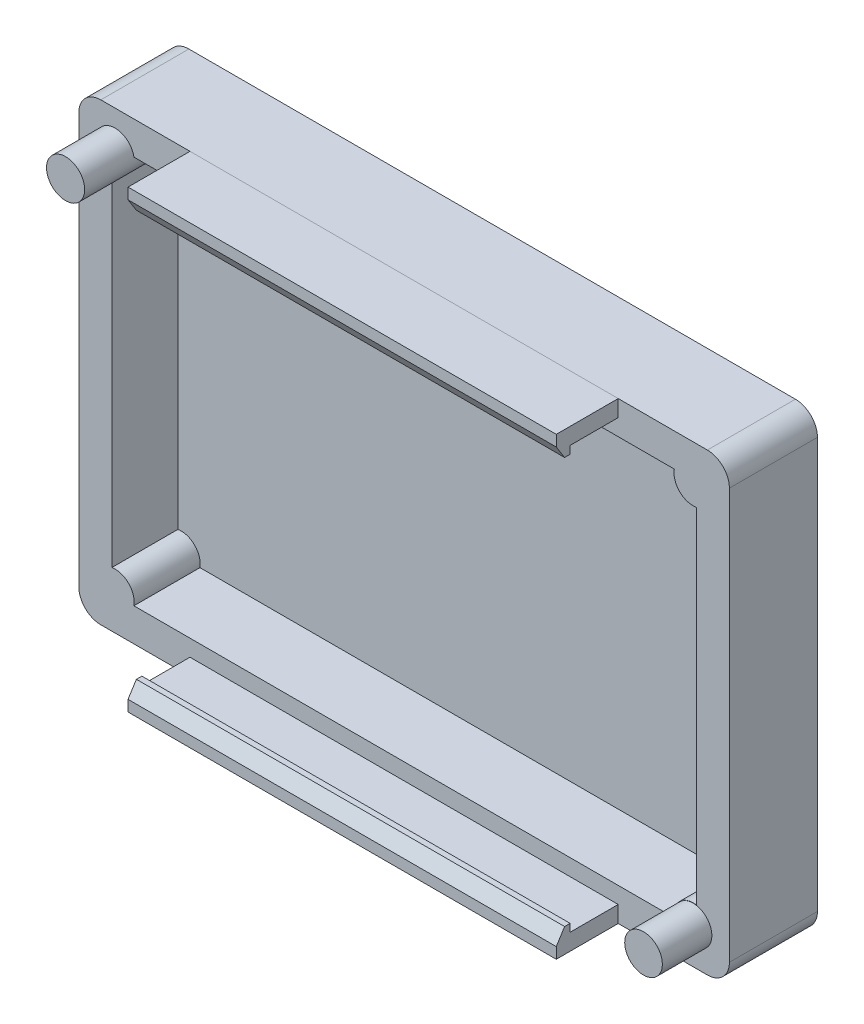
SolidWorks part; units mm, degrees
ref_plane "Płaszczyzna przednia" through (0, 0, 0) normal (0, 0, 1) x (1, 0, 0)
ref_plane "Płaszczyzna górna" through (0, 0, 0) normal (0, 1, 0) x (1, 0, 0)
ref_plane "Płaszczyzna prawa" through (0, 0, 0) normal (1, 0, 0) x (0, 0, -1)
sketch "Szkic1" plane through (0, 0, 48.1425) normal (0, 0, -1) x (-1, 0, 0)
  line L0 (25.6891, 14.5045) -> (25.6891, -16.1313) construction
  line L1 (23.6569, -18.1633) -> (-24.7789, -18.1633) construction
  line L2 (-26.8109, -16.1315) -> (-26.8109, 14.5047) construction
  line L3 (-24.7791, 16.5367) -> (23.6571, 16.5367) construction
  line L4 (25.6891, 14.5045) -> (25.6891, -16.1313)
  line L5 (23.6569, -18.1633) -> (-24.7789, -18.1633)
  line L6 (-26.8109, -16.1315) -> (-26.8109, 14.5047)
  line L7 (-24.7791, 16.5367) -> (23.6571, 16.5367)
  line L8 (-25.1053, 16.8367) -> (23.9833, 16.8367)
  line L9 (25.9891, 14.8307) -> (25.9891, -16.4575)
  line L10 (23.9831, -18.4633) -> (-25.1051, -18.4633)
  line L11 (-27.1109, -16.4577) -> (-27.1109, 14.8309)
  line L13 (-30.1109, -21.4633) -> (28.9891, -21.4633)
  line L14 (-30.1109, -21.4633) -> (-30.1109, 19.8367)
  line L15 (-30.1109, 19.8367) -> (28.9891, 19.8367)
  line L16 (28.9891, -21.4633) -> (28.9891, 19.8367)
  arc A0 (23.6571, 16.5367) -> (25.6891, 14.5045) centre (25.6891, 16.5365) ccw construction
  arc A1 (25.6891, -16.1313) -> (23.6569, -18.1633) centre (25.6891, -18.1635) ccw construction
  arc A2 (-24.7789, -18.1633) -> (-26.8109, -16.1315) centre (-26.8109, -18.1635) ccw construction
  arc A3 (-26.8109, 14.5047) -> (-24.7791, 16.5367) centre (-26.8109, 16.5365) ccw construction
  arc A4 (23.6571, 16.5367) -> (25.6891, 14.5045) centre (25.6891, 16.5365) ccw
  arc A5 (25.6891, -16.1313) -> (23.6569, -18.1633) centre (25.6891, -18.1635) ccw
  arc A6 (-24.7789, -18.1633) -> (-26.8109, -16.1315) centre (-26.8109, -18.1635) ccw
  arc A7 (-26.8109, 14.5047) -> (-24.7791, 16.5367) centre (-26.8109, 16.5365) ccw
  arc A8 (23.9833, 16.8367) -> (25.9891, 14.8307) centre (25.6891, 16.5365) ccw
  arc A9 (25.9891, -16.4575) -> (23.9831, -18.4633) centre (25.6891, -18.1635) ccw
  arc A10 (-25.1051, -18.4633) -> (-27.1109, -16.4577) centre (-26.8109, -18.1635) ccw
  arc A11 (-27.1109, 14.8309) -> (-25.1053, 16.8367) centre (-26.8109, 16.5365) ccw
  dimension "D2" = 3
  dimension "D3" = 3
  dimension "D4" = 3
  dimension "D5" = 3
  dimension "D1" = 0.3
extrude "Dodanie-wyciągnięcie1" add sketch "Szkic1" against normal blind 6 contours L13 L16 L15 L14 L11 A11 L8 A8 L9 A9 L10 A10 region at (29.3899, -0.8133, 48.1425)
sketch "Szkic2" plane through (0, 0, 48.1425) normal (0, 0, -1) x (-1, 0, 0)
  line L1 (-30.1109, 19.8367) -> (28.9891, 19.8367)
  line L2 (-30.1109, 19.8367) -> (-30.1109, -21.4633)
  line L3 (-30.1109, -21.4633) -> (28.9891, -21.4633)
  line L4 (28.9891, 19.8367) -> (28.9891, -21.4633)
extrude "Dodanie-wyciągnięcie2" add sketch "Szkic2" along normal blind 2
sketch "Szkic5" plane through (30.1109, 0, 0) normal (1, 0, 0) x (0, 0, -1)
  line L0 (-54.1425, 19.8367) -> (-59.7689, 19.8367)
  line L1 (-59.7689, 19.8367) -> (-59.7689, 18.8367)
  line L3 (-58.5127, 17.6367) -> (-58.5127, 18.3367)
  line L4 (-58.5127, 18.3367) -> (-54.1425, 18.3367)
  line L5 (-54.1425, -21.4633) -> (-54.1425, 19.8367) construction
  line L6 (-58.5127, 17.6367) -> (-59.0127, 17.6367)
  line L7 (-59.0127, 17.6367) -> (-59.7689, 18.8367)
  line L8 (-54.1425, 18.3367) -> (-54.1425, 19.8367)
  dimension "D1" = 1
  dimension "D2" = 0.7
  dimension "D3" = 5.6264
  dimension "D4" = 1.5
  dimension "D5" = 0.5
extrude "Dodanie-wyciągnięcie3" add sketch "Szkic5" against normal blind 49
extrude "Wytnij-wyciągnięcie2" cut sketch "Szkic5<2>" against normal blind 10.1
sketch "Szkic5<2>" plane through (30.1109, 0, 0) normal (1, 0, 0) x (0, 0, -1) same geometry as "Szkic5"
ref_point "Punkt1"
ref_axis "Oś1" through (30.1109, 19.8367, 54.1425) along (0, 0, -1)
ref_point "Punkt2"
ref_axis "Oś2" through (30.1109, -0.8133, 50.1425) along (0, 0, -1)
ref_plane "Płaszczyzna1" through (0, -0.8133, 0) normal (0, -1, 0) x (0, 0, -1)
mirror "Lustro3" about plane through (0, -0.8133, 0) normal (0, -1, 0) of bodies 105
sketch "Szkic10" plane through (0, 0, 54.1425) normal (0, 0, 1) x (1, 0, 0)
  circle A2 centre (26.8109, -18.1635) radius 1.7089
  circle A3 centre (-25.6891, 16.5365) radius 1.732
extrude "Dodanie-wyciągnięcie4" add sketch "Szkic10" along normal blind 4.5
fillet "Zaokrąglenie2" radius 2 4 edges at (-28.9891, 19.8367, 50.1425) (30.1109, 19.8367, 50.1425) (30.1109, -21.4633, 50.1425) (-28.9891, -21.4633, 50.1425)
